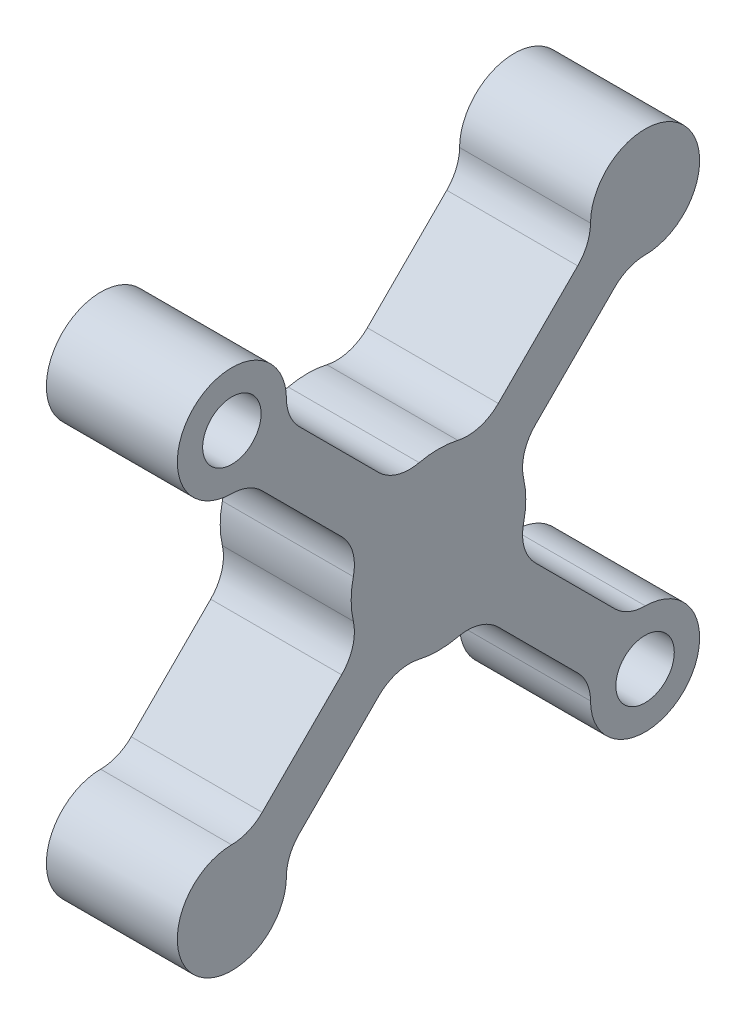
SolidWorks part; units mm, degrees
ref_plane "Front Plane" through (0, 0, 0) normal (1, 0, 0) x (0, 1, 0)
ref_plane "Top Plane" through (0, 0, 0) normal (0, 0, 1) x (0, 1, 0)
ref_plane "Right Plane" through (0, 0, 0) normal (0, 1, 0) x (-1, 0, 0)
sketch "Sketch1" plane through (0, 0, 0) normal (1, 0, 0) x (0, 1, 0)
  line L0 (12.0208, -12.0208) -> (-12.0208, 12.0208) construction
  line L1 (-12.0208, -12.0208) -> (12.0208, 12.0208) construction
  line L2 (0, 0) -> (9.1306, 0) construction
  point P4 (0, 0)
  point P7 (0, 0)
  dimension "D1" = 34
  dimension "D2" = 45
sketch "Sketch2" plane through (0, 0, 0) normal (1, 0, 0) x (0, 1, 0)
  line L0 (12.0208, -12.0208) -> (-12.0208, 12.0208) construction
  line L5 (-8.102, 10.2572) -> (-3.4802, 5.6355)
  line L6 (-12.0208, 12.0208) -> (0, 0) construction
  line L7 (-10.2572, 8.102) -> (-5.6355, 3.4802)
  line L8 (10.2572, 8.102) -> (5.6355, 3.4802)
  line L9 (8.102, 10.2572) -> (3.4802, 5.6355)
  line L10 (8.102, -10.2572) -> (3.4802, -5.6355)
  line L11 (10.2572, -8.102) -> (5.6355, -3.4802)
  line L12 (-10.2572, -8.102) -> (-5.6355, -3.4802)
  line L13 (-8.102, -10.2572) -> (-3.4802, -5.6355)
  circle A0 centre (-12.0208, 12.0208) radius 3.175
  circle A1 centre (12.0208, 12.0208) radius 3.175
  circle A2 centre (12.0208, -12.0208) radius 3.175
  circle A3 centre (-12.0208, -12.0208) radius 3.175
  circle A4 centre (0, 0) radius 5.08
  arc A5 (-8.8459, 12.0388) -> (-8.102, 10.2572) centre (-6.3059, 12.0533) ccw
  arc A6 (-5.6355, 3.4802) -> (-4.9544, 1.1228) centre (-7.4315, 1.6842) cw
  arc A7 (-12.0388, 8.8459) -> (-10.2572, 8.102) centre (-12.0533, 6.3059) cw
  arc A8 (-3.4802, 5.6355) -> (-1.1228, 4.9544) centre (-1.6842, 7.4315) ccw
  arc A9 (12.0388, 8.8459) -> (10.2572, 8.102) centre (12.0533, 6.3059) ccw
  arc A10 (5.6355, 3.4802) -> (4.9544, 1.1228) centre (7.4315, 1.6842) ccw
  arc A11 (8.8459, 12.0388) -> (8.102, 10.2572) centre (6.3059, 12.0533) cw
  arc A12 (3.4802, 5.6355) -> (1.1228, 4.9544) centre (1.6842, 7.4315) cw
  arc A13 (8.8459, -12.0388) -> (8.102, -10.2572) centre (6.3059, -12.0533) ccw
  arc A14 (3.4802, -5.6355) -> (1.1228, -4.9544) centre (1.6842, -7.4315) ccw
  arc A15 (12.0388, -8.8459) -> (10.2572, -8.102) centre (12.0533, -6.3059) cw
  arc A16 (5.6355, -3.4802) -> (4.9544, -1.1228) centre (7.4315, -1.6842) cw
  arc A17 (-12.0388, -8.8459) -> (-10.2572, -8.102) centre (-12.0533, -6.3059) ccw
  arc A18 (-5.6355, -3.4802) -> (-4.9544, -1.1228) centre (-7.4315, -1.6842) ccw
  arc A19 (-8.8459, -12.0388) -> (-8.102, -10.2572) centre (-6.3059, -12.0533) cw
  arc A20 (-3.4802, -5.6355) -> (-1.1228, -4.9544) centre (-1.6842, -7.4315) cw
  point P20 (-5.7911, 7.9464)
  dimension "D1" = 6.35
  dimension "D2" = 10.16
  dimension "D3" = 2.54
  dimension "D4" = 2.54
  dimension "D5" = 1.524
  dimension "D6" = 4
extrude "Boss-Extrude1" add sketch "Sketch2" along normal blind 7.62 contours A0 | A0 L6 A4 A8 L5 A5 | A4 | L9 A12 A4 A10 L8 A9 A1 A11 | A1 | A2 | L11 A16 A4 A14 L10 A13 A2 A15 | L13 A20 A4 A18 L12 A17 A3 A19 | A3 | L6 A0 A7 L7 A6 A4 region at (0, -6.0863, 7.2321) region at (0, -8.9356, 12.0296) region at (0, 0, 4.9363) region at (0, -7.2321, 6.0863) region at (0, 6.6592, 6.6592) region at (0, -6.6592, -6.6592) region at (0, 6.6592, -6.6592) region at (0, 12.0208, 12.0208) region at (0, -12.0208, -12.0208) region at (0, 12.0208, -12.0208)
hole_wizard "M3 Clearance Hole1" positions "Sketch3" profile "Sketch4" hole size "M3" standard "ANSI Metric" end condition through all
sketch "Sketch3" plane through (7.62, 0, 0) normal (1, 0, 0) x (0, 0, -1)
  point P0 (-12.0208, 12.0208)
  point P3 (12.0208, -12.0208)
sketch "Sketch4" plane through (7.62, 12.0208, 12.0208) normal (0, 1, 0) x (0, 0, -1)
  line L0 (0, 0) -> (0, 7.62)
  line L1 (0, 7.62) -> (1.7, 7.62)
  line L2 (1.7, 7.62) -> (1.7, 0)
  line L5 (1.7, 0) -> (0, 0)
  line L11 (0, -6.35) -> (0, 107.95) construction
  dimension "Thru Hole Dia." = 3.4
  dimension "Thru Hole Depth" = 7.62
equation "\"D1@Sketch1\"=34mm"
